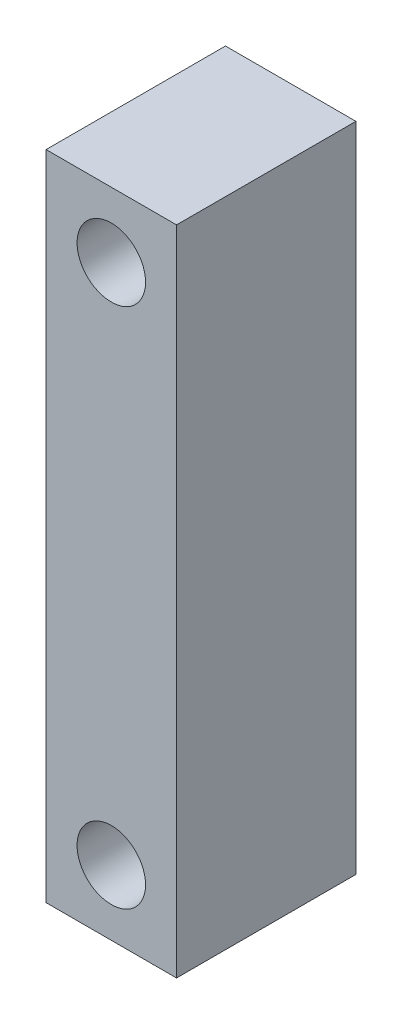
SolidWorks part; units mm, degrees
material "ﾁｰｸ材"
ref_plane "正面" through (0, 0, 0) normal (0, 0, 1) x (1, 0, 0)
ref_plane "平面" through (0, 0, 0) normal (0, 1, 0) x (1, 0, 0)
ref_plane "右側面" through (0, 0, 0) normal (1, 0, 0) x (0, 0, -1)
sketch "ｽｹｯﾁ1" plane through (0, 0, 0) normal (0, 0, 1) x (1, 0, 0)
  line L1 (2, 10) -> (-2, 10)
  line L2 (2, 10) -> (2, -10)
  line L3 (2, -10) -> (-2, -10)
  line L4 (-2, 10) -> (-2, -10)
  line L5 (2, 10) -> (-2, -10) construction
  line L6 (2, -10) -> (-2, 10) construction
  point P0 (0, 0)
  dimension "D1" = 20
  dimension "D2" = 4
extrude "ﾎﾞｽ - 押し出し1" add sketch "ｽｹｯﾁ1" along normal blind 5.5
sketch "ｽｹｯﾁ2" plane through (0, 0, 5.5) normal (0, 0, 1) x (1, 0, 0)
  circle A0 centre (0, 8) radius 1.05
  circle A1 centre (0, -8) radius 1.05
  point P4 (0, 0)
  dimension "D1" = 2.1
  dimension "D2" = 8
  dimension "D3" = 8
extrude "ｶｯﾄ - 押し出し1" cut sketch "ｽｹｯﾁ2" against normal through all
